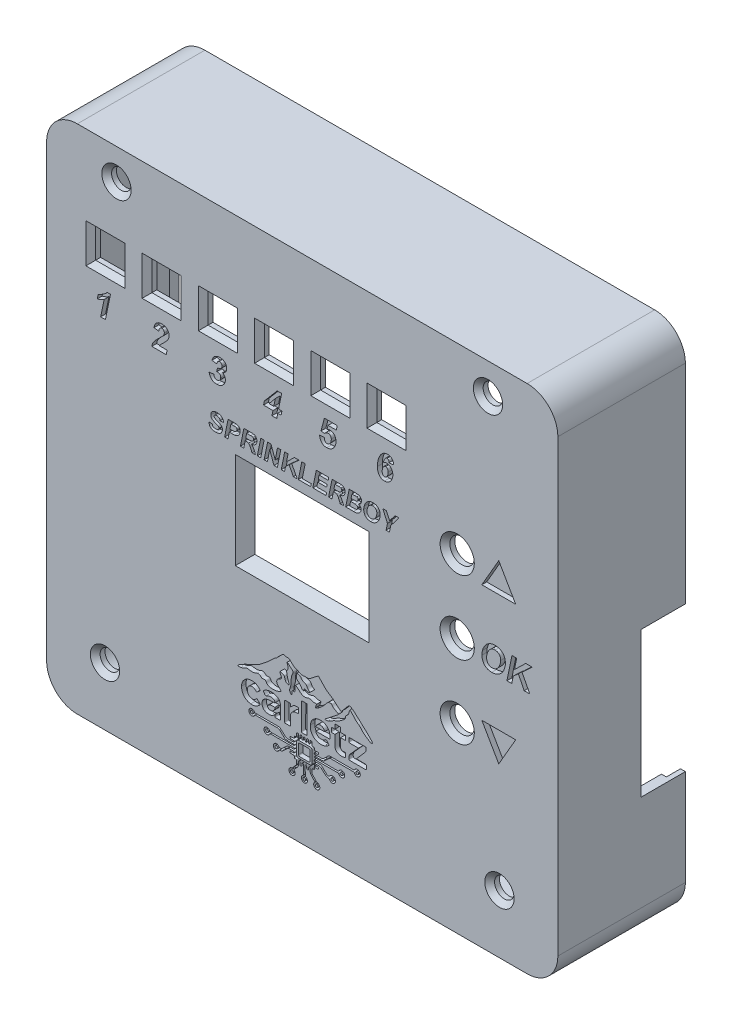
SolidWorks part; units mm, degrees
ref_plane "Front Plane" through (0, 0, 0) normal (0, 0, 1) x (1, 0, 0)
ref_plane "Top Plane" through (0, 0, 0) normal (0, 1, 0) x (1, 0, 0)
ref_plane "Right Plane" through (0, 0, 0) normal (1, 0, 0) x (0, 0, -1)
sketch "Sketch1" plane through (0, 0, 107.9354) normal (0, 0, 1) x (1, 0, 0)
  line L0 (-17.9008, 110.3032) -> (74.0994, 110.3032) construction
  line L1 (80.3867, 104.0159) -> (80.3867, 61.3601) construction
  line L2 (-24.1881, 12.0157) -> (-24.1881, 104.0159) construction
  line L3 (-13.5528, 5.7284) -> (-17.9008, 5.7284) construction
  line L6 (-17.9008, 110.3032) -> (74.0994, 110.3032)
  line L7 (80.3867, 104.0159) -> (80.3867, 61.3601)
  line L8 (-24.1881, 12.0157) -> (-24.1881, 104.0159)
  line L9 (-13.5528, 5.7284) -> (-17.9008, 5.7284)
  line L13 (80.3867, 31.6547) -> (80.3867, 12.0157) construction
  line L14 (80.3867, 31.6547) -> (80.3867, 12.0157)
  line L15 (-13.5528, 5.7284) -> (69.2377, 5.7284) construction
  line L16 (-13.5528, 5.7284) -> (69.2377, 5.7284)
  line L17 (80.3867, 31.6547) -> (80.3867, 61.3601) construction
  line L18 (80.3867, 31.6547) -> (80.3867, 61.3601)
  line L19 (74.0994, 5.7284) -> (69.2377, 5.7284) construction
  line L20 (74.0994, 5.7284) -> (69.2377, 5.7284)
  arc A0 (80.3867, 104.0159) -> (74.0994, 110.3032) centre (74.0994, 104.0159) ccw construction
  arc A1 (-17.9008, 110.3032) -> (-24.1881, 104.0159) centre (-17.9008, 104.0159) ccw construction
  arc A2 (-24.1881, 12.0157) -> (-17.9008, 5.7284) centre (-17.9008, 12.0157) ccw construction
  arc A4 (80.3867, 104.0159) -> (74.0994, 110.3032) centre (74.0994, 104.0159) ccw
  arc A5 (-17.9008, 110.3032) -> (-24.1881, 104.0159) centre (-17.9008, 104.0159) ccw
  arc A6 (-24.1881, 12.0157) -> (-17.9008, 5.7284) centre (-17.9008, 12.0157) ccw
  arc A8 (74.0994, 5.7284) -> (80.3867, 12.0157) centre (74.0994, 12.0157) ccw construction
  arc A9 (74.0994, 5.7284) -> (80.3867, 12.0157) centre (74.0994, 12.0157) ccw
extrude "Boss-Extrude1" add sketch "Sketch1" along normal blind 2
sketch "Sketch3" plane through (0, 0, 107.9354) normal (0, 0, -1) x (-1, 0, 0)
  line L13 (24.1881, 104.0159) -> (24.1881, 12.0157) construction
  line L14 (17.9008, 5.7284) -> (-74.0994, 5.7284) construction
  line L15 (-80.3867, 12.0157) -> (-80.3867, 104.0159) construction
  line L16 (-74.0994, 110.3032) -> (17.9008, 110.3032) construction
  line L17 (24.1881, 104.0159) -> (24.1881, 12.0157)
  line L18 (17.9008, 5.7284) -> (-74.0994, 5.7284)
  line L19 (-80.3867, 12.0157) -> (-80.3867, 104.0159)
  line L20 (-74.0994, 110.3032) -> (17.9008, 110.3032)
  line L21 (-74.0994, 108.3032) -> (17.9008, 108.3032)
  line L22 (22.1881, 104.0159) -> (22.1881, 12.0157)
  line L23 (17.9008, 7.7284) -> (-74.0994, 7.7284)
  line L24 (-78.3867, 12.0157) -> (-78.3867, 104.0159)
  arc A12 (24.1881, 104.0159) -> (17.9008, 110.3032) centre (17.9008, 104.0159) ccw construction
  arc A13 (17.9008, 5.7284) -> (24.1881, 12.0157) centre (17.9008, 12.0157) ccw construction
  arc A14 (-80.3867, 12.0157) -> (-74.0994, 5.7284) centre (-74.0994, 12.0157) ccw construction
  arc A15 (-74.0994, 110.3032) -> (-80.3867, 104.0159) centre (-74.0994, 104.0159) ccw construction
  arc A16 (24.1881, 104.0159) -> (17.9008, 110.3032) centre (17.9008, 104.0159) ccw
  arc A17 (17.9008, 5.7284) -> (24.1881, 12.0157) centre (17.9008, 12.0157) ccw
  arc A18 (-80.3867, 12.0157) -> (-74.0994, 5.7284) centre (-74.0994, 12.0157) ccw
  arc A19 (-74.0994, 110.3032) -> (-80.3867, 104.0159) centre (-74.0994, 104.0159) ccw
  arc A20 (22.1881, 104.0159) -> (17.9008, 108.3032) centre (17.9008, 104.0159) ccw
  arc A21 (17.9008, 7.7284) -> (22.1881, 12.0157) centre (17.9008, 12.0157) ccw
  arc A22 (-78.3867, 12.0157) -> (-74.0994, 7.7284) centre (-74.0994, 12.0157) ccw
  arc A23 (-74.0994, 108.3032) -> (-78.3867, 104.0159) centre (-74.0994, 104.0159) ccw
  dimension "D1" = 2
extrude "Boss-Extrude2" add sketch "Sketch3" along normal up to surface (21.1862 mm away)
sketch "Sketch4" plane through (0, 0, 109.9354) normal (0, 0, 1) x (1, 0, 0)
  circle A0 centre (-9.9008, 104.0159) radius 2
  circle A1 centre (66.0994, 104.0159) radius 2
  circle A2 centre (68.4425, 17.6725) radius 2
  circle A3 centre (-12.244, 17.6725) radius 1.998
extrude "Cut-Extrude1" cut sketch "Sketch4" against normal up to next
sketch "Sketch5" plane through (0, 0, 109.9354) normal (0, 0, 1) x (1, 0, 0)
  line L0 (39.2941, 65.3848) -> (16.9045, 65.3848) construction
  line L1 (16.9045, 65.3848) -> (39.2941, 65.3848)
  line L2 (16.9045, 65.3848) -> (16.9045, 50.6848)
  line L3 (16.9045, 50.6848) -> (39.2941, 50.6848)
  line L4 (39.2941, 65.3848) -> (39.2941, 50.6848)
  line L5 (16.9045, 65.3848) -> (16.9045, 50.6848) construction
  line L6 (16.9045, 50.6848) -> (39.2941, 50.6848) construction
extrude "Cut-Extrude2" cut sketch "Sketch5" against normal up to next
chamfer "Chamfer1" distance 2.5 angle 45 4 edges at (28.0993, 50.6848, 109.9354) (39.2941, 58.0348, 109.9354) (16.9045, 58.0348, 109.9354) (28.0993, 65.3848, 109.9354)
sketch "Sketch7" plane through (80.3867, 0, 0) normal (1, 0, 0) x (0, 0, -1)
  line L0 (-92.9354, 104.0159) -> (-92.9354, 12.0157) construction
  line L1 (-92.9354, 31.6547) -> (-75.9354, 31.6547)
  line L2 (-92.9354, 31.6547) -> (-92.9354, 61.3601)
  line L3 (-92.9354, 61.3601) -> (-75.9354, 61.3601)
  line L4 (-75.9354, 31.6547) -> (-75.9354, 61.3601)
  line L5 (-83.5354, 31.7547) -> (-91.3354, 31.7547) construction
  line L6 (-83.5354, 61.2601) -> (-91.3354, 61.2601) construction
  dimension "D1" = 17
  dimension "D2" = 0.1
  dimension "D3" = 0.1
extrude "Cut-Extrude4" cut sketch "Sketch7" against normal up to next
sketch "Sketch8" plane through (0, 5.7284, 0) normal (0, -1, 0) x (1, 0, 0)
  line L0 (74.0994, 86.7492) -> (-17.9008, 86.7492) construction
  line L1 (-13.5528, 86.7492) -> (51.7933, 86.7492)
  line L2 (-13.5528, 86.7492) -> (-13.5528, 90.2354)
  line L3 (-13.5528, 90.2354) -> (51.7933, 90.2354)
  line L4 (51.7933, 86.7492) -> (51.7933, 90.2354)
  line L5 (-13.5528, 83.7492) -> (-13.5528, 73.2354) construction
  line L6 (51.6933, 81.1633) -> (51.6933, 73.3354) construction
  line L7 (-13.5528, 73.2354) -> (69.2377, 73.2354) construction
  dimension "D1" = 0.1
  dimension "D2" = 17
extrude "Cut-Extrude5" cut sketch "Sketch8" against normal up to next and the other way through all
sketch "Sketch9" plane through (0, 0, 109.9354) normal (0, 0, 1) x (1, 0, 0)
  line L0 (-15.0508, 92.6158) -> (-15.0508, 87.4158) construction
  line L1 (-15.1508, 93.0158) -> (-9.1508, 93.0158)
  line L2 (-15.1508, 93.0158) -> (-15.1508, 87.0158)
  line L3 (-15.1508, 87.0158) -> (-9.1508, 87.0158)
  line L4 (-9.1508, 93.0158) -> (-9.1508, 87.0158)
  line L5 (-14.7508, 87.1158) -> (-9.5508, 87.1158) construction
  line L6 (-9.2508, 87.4158) -> (-9.2508, 92.6158) construction
  line L7 (-9.5508, 92.9158) -> (-14.7508, 92.9158) construction
  line L8 (1.9492, 92.9158) -> (-3.2508, 92.9158) construction
  line L9 (-3.6508, 93.0158) -> (2.3492, 93.0158)
  line L10 (-3.6508, 93.0158) -> (-3.6508, 87.0158)
  line L11 (-3.6508, 87.0158) -> (2.3492, 87.0158)
  line L12 (2.3492, 93.0158) -> (2.3492, 87.0158)
  line L13 (-3.5508, 92.6158) -> (-3.5508, 87.4158) construction
  line L14 (-3.2508, 87.1158) -> (1.9492, 87.1158) construction
  line L15 (2.2492, 87.4158) -> (2.2492, 92.6158) construction
  line L16 (7.9492, 92.6158) -> (7.9492, 87.4158) construction
  line L17 (7.8492, 93.0158) -> (13.8492, 93.0158)
  line L18 (7.8492, 93.0158) -> (7.8492, 87.0158)
  line L19 (7.8492, 87.0158) -> (13.8492, 87.0158)
  line L20 (13.8492, 93.0158) -> (13.8492, 87.0158)
  line L21 (13.4492, 92.9158) -> (8.2492, 92.9158) construction
  line L22 (13.7492, 87.4158) -> (13.7492, 92.6158) construction
  line L23 (8.2492, 87.1158) -> (13.4492, 87.1158) construction
  line L24 (24.9493, 92.9158) -> (19.7493, 92.9158) construction
  line L25 (19.3493, 93.0158) -> (25.3493, 93.0158)
  line L26 (19.3493, 93.0158) -> (19.3493, 87.0158)
  line L27 (19.3493, 87.0158) -> (25.3493, 87.0158)
  line L28 (25.3493, 93.0158) -> (25.3493, 87.0158)
  line L29 (19.4493, 92.6158) -> (19.4493, 87.4158) construction
  line L30 (19.7493, 87.1158) -> (24.9493, 87.1158) construction
  line L31 (25.2493, 87.4158) -> (25.2493, 92.6158) construction
  line L32 (36.4493, 92.9158) -> (31.2493, 92.9158) construction
  line L33 (30.8493, 93.0158) -> (36.8493, 93.0158)
  line L34 (30.8493, 93.0158) -> (30.8493, 87.0158)
  line L35 (30.8493, 87.0158) -> (36.8493, 87.0158)
  line L36 (36.8493, 93.0158) -> (36.8493, 87.0158)
  line L37 (42.3493, 93.0158) -> (48.3493, 93.0158)
  line L38 (42.3493, 93.0158) -> (42.3493, 87.0158)
  line L39 (42.3493, 87.0158) -> (48.3493, 87.0158)
  line L40 (48.3493, 93.0158) -> (48.3493, 87.0158)
  line L41 (36.7493, 87.4158) -> (36.7493, 92.6158) construction
  line L42 (31.2493, 87.1158) -> (36.4493, 87.1158) construction
  line L43 (30.9493, 92.6158) -> (30.9493, 87.4158) construction
  line L44 (42.4493, 92.6158) -> (42.4493, 87.4158) construction
  line L45 (42.7493, 87.1158) -> (47.9493, 87.1158) construction
  line L46 (48.2493, 87.4158) -> (48.2493, 92.6158) construction
  line L47 (47.9493, 92.9158) -> (42.7493, 92.9158) construction
  dimension "D1" = 0.1
  dimension "D2" = 0.1
  dimension "D3" = 0.1
  dimension "D4" = 0.1
  dimension "D5" = 0.1
  dimension "D6" = 0.1
  dimension "D7" = 0.1
  dimension "D8" = 0.1
  dimension "D9" = 0.1
  dimension "D10" = 0.1
  dimension "D11" = 0.1
  dimension "D12" = 0.1
  dimension "D13" = 0.1
  dimension "D14" = 0.1
  dimension "D15" = 0.1
  dimension "D16" = 0.1
  dimension "D17" = 0.1
  dimension "D18" = 0.1
  dimension "D19" = 0.1
  dimension "D20" = 0.1
  dimension "D21" = 0.1
  dimension "D22" = 0.1
  dimension "D23" = 0.1
  dimension "D24" = 0.1
extrude "Cut-Extrude6" cut sketch "Sketch9" against normal up to next
sketch "Sketch10" plane through (0, 0, 109.9354) normal (0, 0, 1) x (1, 0, 0)
  circle A0 centre (59.7974, 73.0158) radius 2.5
  circle A1 centre (59.7974, 58.0158) radius 2.5
  circle A2 centre (59.7974, 43.0157) radius 2.5
  arc A3 (62.4474, 75.2658) -> (63.6474, 75.2658) centre (63.0474, 75.2658) ccw construction
  arc A5 (57.1473, 60.2658) -> (55.9473, 60.2658) centre (56.5473, 60.2658) ccw construction
  arc A6 (62.4474, 60.2658) -> (63.6474, 60.2658) centre (63.0474, 60.2658) ccw construction
  arc A7 (57.1473, 40.7657) -> (55.9473, 40.7657) centre (56.5473, 40.7657) ccw construction
  arc A8 (63.6474, 40.7657) -> (62.4474, 40.7657) centre (63.0474, 40.7657) ccw construction
  dimension "D2" = 5
  dimension "D3" = 3.25
  dimension "D4" = 2.25
  dimension "D5" = 3.25
  dimension "D6" = 5
  dimension "D8" = 3.25
  dimension "D9" = 5
  dimension "D1" = 2.25
  dimension "D7" = 2.25
extrude "Cut-Extrude7" cut sketch "Sketch10" against normal up to next
chamfer "Chamfer2" distance 1 angle 45 3 edges at (62.2974, 43.0157, 109.9354) (62.2974, 58.0158, 109.9354) (62.2974, 73.0158, 109.9354)
chamfer "Chamfer3" distance 1 angle 45 24 edges at (48.3493, 90.0158, 109.9354) (45.3493, 93.0158, 109.9354) (42.3493, 90.0158, 109.9354) (45.3493, 87.0158, 109.9354) (33.8493, 87.0158, 109.9354) (36.8493, 90.0158, 109.9354) (33.8493, 93.0158, 109.9354) (30.8493, 90.0158, 109.9354) (25.3493, 90.0158, 109.9354) (22.3493, 93.0158, 109.9354) (19.3493, 90.0158, 109.9354) (22.3493, 87.0158, 109.9354) (10.8492, 87.0158, 109.9354) (13.8492, 90.0158, 109.9354) (10.8492, 93.0158, 109.9354) (7.8492, 90.0158, 109.9354) (2.3492, 90.0158, 109.9354) (-0.6508, 93.0158, 109.9354) (-3.6508, 90.0158, 109.9354) (-0.6508, 87.0158, 109.9354) (-12.1508, 87.0158, 109.9354) (-9.1508, 90.0158, 109.9354) (-12.1508, 93.0158, 109.9354) (-15.1508, 90.0158, 109.9354)
sketch "Sketch11" plane through (0, 0, 109.9354) normal (0, 0, 1) x (1, 0, 0)
  text T0 "OK" font "Arial" height 5
extrude "Cut-Extrude8" cut sketch "Sketch11" against normal blind 1
sketch "Sketch12" plane through (0, 0, 109.9354) normal (0, 0, 1) x (1, 0, 0)
  line L1 (68.2974, 76.0158) -> (64.8332, 70.0158)
  line L2 (64.8332, 70.0158) -> (71.7615, 70.0158)
  line L3 (71.7615, 70.0158) -> (68.2974, 76.0158)
  line L7 (68.2974, 40.0157) -> (71.7615, 46.0157)
  line L8 (71.7615, 46.0157) -> (64.8332, 46.0157)
  line L9 (64.8332, 46.0157) -> (68.2974, 40.0157)
  circle A0 centre (68.2974, 72.0158) radius 2 construction
  circle A1 centre (59.7974, 73.0158) radius 3.5 construction
  circle A2 centre (59.7974, 73.0158) radius 2.5 construction
  circle A4 centre (68.2974, 44.0157) radius 2 construction
  circle A5 centre (59.7974, 43.0157) radius 3.5 construction
  dimension "D2" = 3
  dimension "D1" = 6
  dimension "D3" = 8.5
  dimension "D4" = 6
  dimension "D5" = 3
  dimension "D6" = 8.5
extrude "Cut-Extrude9" cut sketch "Sketch12" against normal blind 1
sketch "Sketch13" plane through (0, 0, 109.9354) normal (0, 0, 1) x (1, 0, 0)
  text T0 "1" font "Arial" height 5
  text T1 "2" font "Arial" height 5
  text T2 "3" font "Arial" height 5
  text T3 "4" font "Arial" height 5
  text T4 "5" font "Arial" height 5
  text T5 "6" font "Arial" height 5
extrude "Cut-Extrude10" cut sketch "Sketch13" against normal blind 1
sketch "Sketch14" plane through (0, 0, 109.9354) normal (0, 0, 1) x (1, 0, 0)
  text T0 "SPRINKLERBOY" font "Arial" height 3.5
extrude "Cut-Extrude12" cut sketch "Sketch14" against normal blind 1
sketch "Schizzo3" plane through (0, 0, 109.9354) normal (0, 0, 1) x (1, 0, 0)
  spline S0 degree 3 poles (28.3707, 32.9624) (28.4003, 33.0508) (28.4309, 33.1328) (28.4554, 33.2167) (28.5202, 33.4376) (28.6287, 33.4812) (28.8265, 33.3629) (29.1577, 33.1648) (29.4064, 33.1809) (29.7538, 33.4451) knots 10 10 10 10 11 11 11 12 12 12 13 13 13 13
  spline S1 degree 3 poles (26.9936, 35.4214) (26.9837, 35.2643) (26.9839, 35.1121) (26.9628, 34.9628) (26.8906, 34.453) (26.9614, 34.2983) (27.4029, 34.0331) (27.4431, 34.0089) (27.487, 33.9828) (27.514, 33.9463) (27.6507, 33.7615) (27.792, 33.579) (27.9129, 33.3841) (28.0243, 33.2047) (28.1215, 33.0208) (28.3707, 32.9624) knots 5 5 5 5 6 6 6 7 7 7 8 8 8 9 9 9 10 10 10 10
  spline S2 degree 3 poles (29.7538, 33.4451) (29.6587, 33.5005) (29.5875, 33.5529) (29.5083, 33.5858) (29.3144, 33.6662) (29.1873, 33.8094) (29.1235, 34.0017) (29.0268, 34.2938) (28.8358, 34.4717) (28.5351, 34.5303) (28.2311, 34.5895) (28.0208, 34.7588) (27.865, 35.0288) (27.6895, 35.3328) (27.3113, 35.4806) (26.9936, 35.4214) knots 0 0 0 0 1 1 1 2 2 2 3 3 3 4 4 4 5 5 5 5
  spline S3 degree 3 poles (30.831, 31.2383) (30.8323, 31.2978) (30.8196, 31.3619) (30.8376, 31.4158) (30.894, 31.5846) (30.9619, 31.7496) (31.0421, 31.9596) knots 117 117 117 117 118 118 118 119 119 119 119
  spline S4 degree 3 poles (32.6948, 30.1787) (32.9278, 30.3418) (33.1268, 30.4678) (33.3111, 30.6126) (33.9753, 31.1341) (34.6377, 31.6579) (35.294, 32.1893) (35.5595, 32.4043) (35.5368, 32.4708) (35.2345, 32.6224) (34.9868, 32.7465) (34.7415, 32.882) (34.5168, 33.0428) (34.3753, 33.1441) (34.2606, 33.2919) (34.1587, 33.4363) (34.0838, 33.5424) (34.0024, 33.5842) (33.8814, 33.5706) (33.5343, 33.5316) (33.2487, 33.381) (33.0363, 33.1007) (32.9598, 32.9998) (32.895, 32.8893) (32.8122, 32.7942) (32.6712, 32.6322) (32.5268, 32.472) (32.3719, 32.3234) (32.1247, 32.0861) (31.8767, 31.8482) (31.612, 31.6312) (31.431, 31.4829) (31.2245, 31.3642) (31.0219, 31.2451) (30.9737, 31.2167) (30.8954, 31.2392) (30.831, 31.2383) knots 105 105 105 105 106 106 106 107 107 107 108 108 108 109 109 109 110 110 110 111 111 111 112 112 112 113 113 113 114 114 114 115 115 115 116 116 116 117 117 117 117
  spline S5 degree 3 poles (37.8726, 34.3603) (37.8012, 34.174) (37.7274, 34.04) (37.6995, 33.897) (37.633, 33.5555) (37.4795, 33.2818) (37.1986, 33.0664) (37.0944, 32.9864) (36.9837, 32.8424) (36.9766, 32.7216) (36.954, 32.341) (36.7284, 32.1032) (36.467, 31.8835) (35.9887, 31.4816) (35.4676, 31.1584) (34.8747, 30.938) (34.5034, 30.8) (34.1637, 30.5761) (33.8117, 30.3873) (33.5272, 30.2347) (33.2382, 30.0971) (32.9057, 30.105) (32.8479, 30.1064) (32.7911, 30.1438) (32.6948, 30.1787) knots 97 97 97 97 98 98 98 99 99 99 100 100 100 101 101 101 102 102 102 103 103 103 104 104 104 105 105 105 105
  spline S6 degree 3 poles (31.3954, 37.1477) (31.7741, 36.7468) (32.1481, 36.3525) (32.5203, 35.9566) (32.9469, 35.5029) (33.4309, 35.1296) (33.9813, 34.8319) (34.2372, 34.6935) (34.4614, 34.4905) (34.6844, 34.2987) (35.0525, 33.982) (35.4011, 33.6424) (35.7714, 33.3285) (35.9749, 33.156) (36.0519, 33.1572) (36.2299, 33.3549) (36.4941, 33.6484) (36.7256, 33.9712) (36.9797, 34.2743) (37.1593, 34.4887) (37.3469, 34.6973) (37.5427, 34.8969) (37.6919, 35.0489) (37.8383, 35.0762) (38.0153, 34.9617) (38.2891, 34.7847) (38.5633, 34.6009) (38.8059, 34.3846) (39.6068, 33.6705) (40.3977, 32.9449) (41.1839, 32.2145) (41.5158, 31.9061) (41.8292, 31.5777) (42.1448, 31.2522) (42.2505, 31.1432) (42.348, 31.0223) (42.4291, 30.894) (42.5195, 30.7511) (42.4534, 30.6351) (42.2881, 30.6449) (42.1704, 30.6518) (42.0371, 30.6677) (41.9413, 30.728) (41.3164, 31.1219) (40.6855, 31.513) (40.1911, 32.0743) (39.9962, 32.2955) (39.8402, 32.55) (39.5805, 32.7098) (39.4147, 32.8118) (39.2326, 32.9024) (39.0989, 33.0386) (38.8189, 33.3238) (38.5689, 33.6384) (38.3006, 33.9355) (38.1789, 34.0703) (38.0429, 34.1923) (37.8726, 34.3603) knots 78 78 78 78 79 79 79 80 80 80 81 81 81 82 82 82 83 83 83 84 84 84 85 85 85 86 86 86 87 87 87 88 88 88 89 89 89 90 90 90 91 91 91 92 92 92 93 93 93 94 94 94 95 95 95 96 96 96 97 97 97 97
  spline S7 degree 3 number of poles 172 (25.0103, 36.3727) -> (31.3954, 37.1477)
  spline S8 degree 3 poles (25.9032, 31.065) (25.5886, 31.2528) (25.4281, 31.6472) (25.5642, 31.9828) (25.742, 32.4214) (25.8228, 32.8688) (25.7908, 33.3403) (25.7837, 33.4437) (25.8098, 33.5495) (25.8227, 33.6539) (25.8531, 33.8991) (25.8653, 34.1486) (25.9218, 34.3876) (25.968, 34.5835) (26.0591, 34.7706) (26.1453, 34.9546) (26.2792, 35.2402) (26.2673, 35.3458) (26.0378, 35.5504) (25.7777, 35.7823) (25.5166, 36.013) (25.2516, 36.2392) (25.196, 36.2866) (25.1217, 36.3122) (25.0103, 36.3727) knots 13 13 13 13 14 14 14 15 15 15 16 16 16 17 17 17 18 18 18 19 19 19 20 20 20 21 21 21 21
  spline S9 degree 3 poles (26.223, 32.0099) (26.03, 31.8279) (25.9736, 31.6084) (26.0018, 31.3591) (26.0144, 31.2469) (26.0236, 31.1337) (25.9032, 31.065) knots 11 11 11 11 12 12 12 13 13 13 13
  spline S10 degree 3 poles (31.0421, 31.9596) (30.9082, 31.9759) (30.7944, 32.0097) (30.6851, 31.9987) (30.4678, 31.9768) (30.2632, 32.0052) (30.0704, 32.1015) (29.7739, 32.2496) (29.4735, 32.2673) (29.1711, 32.1341) (28.5234, 31.8488) (28.0101, 32.0981) (27.5349, 32.5282) (27.3394, 32.7052) (27.1395, 32.8791) (26.9285, 33.0369) (26.7405, 33.1775) (26.629, 33.1179) (26.6158, 32.8795) (26.6056, 32.6949) (26.6168, 32.5092) (26.6113, 32.3242) (26.6078, 32.2084) (26.6009, 32.0909) (26.576, 31.9785) (26.5631, 31.9204) (26.5107, 31.8312) (26.471, 31.8283) (26.4139, 31.8242) (26.3495, 31.8824) (26.2935, 31.9215) (26.265, 31.9413) (26.248, 31.9775) (26.223, 32.0099) knots 0 0 0 0 1 1 1 2 2 2 3 3 3 4 4 4 5 5 5 6 6 6 7 7 7 8 8 8 9 9 9 10 10 10 11 11 11 11
  spline S11 degree 3 poles (28.8018, 17.4103) (28.7954, 17.5593) (28.6614, 17.6925) (28.5116, 17.6867) (28.3723, 17.6813) (28.226, 17.608) (28.2541, 17.4266) knots 2 2 2 2 3 3 3 4 4 4 4
  spline S12 degree 3 poles (28.2541, 17.4266) (28.2562, 17.2617) (28.3812, 17.1212) (28.5263, 17.1206) (28.672, 17.1199) (28.8082, 17.2632) (28.8018, 17.4103) knots 0 0 0 0 1 1 1 2 2 2 2
  spline S13 degree 3 poles (22.8204, 19.942) (22.9551, 19.9451) (23.1, 20.0979) (23.0973, 20.2339) (23.0946, 20.3712) (22.9456, 20.5154) (22.808, 20.5137) knots 2 2 2 2 3 3 3 4 4 4 4
  spline S14 degree 3 poles (22.808, 20.5137) (22.6576, 20.5119) (22.5462, 20.3861) (22.5483, 20.2207) (22.5505, 20.055) (22.6644, 19.9383) (22.8204, 19.942) knots 0 0 0 0 1 1 1 2 2 2 2
  spline S15 degree 3 poles (20.613, 22.1633) (20.6143, 22.0216) (20.7553, 21.8784) (20.8941, 21.8779) (21.0477, 21.8773) (21.1819, 22.0023) (21.1848, 22.1487) knots 2 2 2 2 3 3 3 4 4 4 4
  spline S16 degree 3 poles (21.1848, 22.1487) (21.1877, 22.2941) (21.0391, 22.4515) (20.9, 22.4503) (20.7755, 22.4493) (20.6118, 22.2856) (20.613, 22.1633) knots 0 0 0 0 1 1 1 2 2 2 2
  spline S17 degree 3 poles (30.8017, 17.4972) (30.8032, 17.333) (30.9173, 17.213) (31.0734, 17.2117) (31.2166, 17.2106) (31.3422, 17.3453) (31.3441, 17.5023) (31.3459, 17.6554) (31.2189, 17.784) (31.0661, 17.7837) knots 1 1 1 1 2 2 2 3 3 3 4 4 4 4
  spline S18 degree 3 poles (31.0661, 17.7837) (30.9098, 17.7834) (30.8002, 17.6646) (30.8017, 17.4972) knots 0 0 0 0 1 1 1 1
  spline S19 degree 3 poles (25.7242, 17.5144) (25.7193, 17.3486) (25.8416, 17.2118) (25.9945, 17.2118) (26.1422, 17.2118) (26.267, 17.3403) (26.2694, 17.495) knots 2 2 2 2 3 3 3 4 4 4 4
  spline S20 degree 3 poles (26.2694, 17.495) (26.2721, 17.664) (26.1684, 17.7794) (26.009, 17.785) (25.8567, 17.7902) (25.7287, 17.6686) (25.7242, 17.5144) knots 0 0 0 0 1 1 1 2 2 2 2
  spline S21 degree 3 poles (17.7955, 23.6252) (17.9366, 23.6237) (18.0756, 23.7618) (18.0783, 23.9062) (18.0815, 24.0786) (17.9685, 24.1986) (17.8013, 24.2005) knots 2 2 2 2 3 3 3 4 4 4 4
  spline S22 degree 3 poles (17.8013, 24.2005) (17.6517, 24.2022) (17.5347, 24.0877) (17.5309, 23.936) (17.5267, 23.7705) (17.6491, 23.6268) (17.7955, 23.6252) knots 0 0 0 0 1 1 1 2 2 2 2
  spline S23 degree 3 poles (36.1356, 22.4502) (36.0133, 22.4491) (35.8552, 22.2846) (35.8535, 22.1567) (35.8516, 22.014) (35.9874, 21.8799) (36.1372, 21.8765) knots 2 2 2 2 3 3 3 4 4 4 4
  spline S24 degree 3 poles (36.1372, 21.8765) (36.2785, 21.8733) (36.4194, 22.0092) (36.4237, 22.1528) (36.4281, 22.3007) (36.2819, 22.4517) (36.1356, 22.4502) knots 0 0 0 0 1 1 1 2 2 2 2
  spline S25 degree 3 poles (39.6229, 23.9255) (39.6216, 24.0626) (39.489, 24.192) (39.3448, 24.1969) (39.1887, 24.2023) (39.0612, 24.0733) (39.0588, 23.9076) knots 2 2 2 2 3 3 3 4 4 4 4
  spline S26 degree 3 poles (39.0588, 23.9076) (39.0568, 23.7659) (39.1903, 23.6276) (39.3335, 23.6233) (39.4645, 23.6193) (39.6243, 23.7862) (39.6229, 23.9255) knots 0 0 0 0 1 1 1 2 2 2 2
  spline S27 degree 3 poles (34.264, 20.5138) (34.1348, 20.5107) (33.9378, 20.3416) (33.9415, 20.2369) (33.9459, 20.1147) (34.1348, 19.9417) (34.2644, 19.9413) knots 2 2 2 2 3 3 3 4 4 4 4
  spline S28 degree 3 poles (34.2644, 19.9413) (34.4003, 19.9409) (34.5462, 20.0833) (34.5504, 20.2205) (34.555, 20.3703) (34.4114, 20.5174) (34.264, 20.5138) knots 0 0 0 0 1 1 1 2 2 2 2
  spline S29 degree 3 poles (30.0964, 21.3289) (30.0963, 21.969) (30.098, 22.6091) (30.0958, 23.2492) (30.0948, 23.5552) (29.9275, 23.7212) (29.627, 23.7215) (28.8864, 23.7224) (28.1458, 23.7241) (27.4051, 23.7221) (27.1324, 23.7214) (26.9628, 23.5471) (26.9622, 23.2759) (26.9614, 22.8898) (26.962, 22.5036) (26.9621, 22.1174) knots 5 5 5 5 6 6 6 7 7 7 8 8 8 9 9 9 10 10 10 10
  spline S30 degree 3 poles (26.9621, 22.1174) (26.9621, 21.7417) (26.9612, 21.3661) (26.9623, 20.9905) (26.9632, 20.7074) (27.1203, 20.541) (27.3977, 20.5402) (28.1542, 20.5381) (28.9107, 20.5389) (29.6672, 20.5421) (29.9317, 20.5431) (30.0883, 20.699) (30.098, 20.9639) (30.1025, 21.0854) (30.0965, 21.2072) (30.0964, 21.3289) knots 0 0 0 0 1 1 1 2 2 2 3 3 3 4 4 4 5 5 5 5
  spline S31 degree 3 poles (31.1925, 18.134) (31.4324, 18.0711) (31.6546, 17.8443) (31.6913, 17.6133) (31.7343, 17.342) (31.6082, 17.07) (31.3781, 16.938) (31.1661, 16.8164) (30.8748, 16.8372) (30.6772, 16.988) (30.4122, 17.1904) (30.3583, 17.5677) (30.5556, 17.8504) (30.5916, 17.9019) (30.6344, 17.9487) (30.6935, 18.0218) knots 199 199 199 199 200 200 200 201 201 201 202 202 202 203 203 203 204 204 204 204
  spline S32 degree 3 poles (31.4647, 20.7845) (31.4655, 20.6593) (31.3736, 20.5919) (31.2589, 20.5841) (31.1223, 20.5749) (30.984, 20.5847) (30.8468, 20.5929) (30.6049, 20.6073) (30.5825, 20.5887) (30.5815, 20.3482) (30.5807, 20.151) (30.5422, 20.1138) (30.3358, 20.1194) (30.1943, 20.1233) (30.1016, 20.0822) (30.1, 19.9171) (30.0981, 19.7273) (30.0643, 19.5358) (30.0821, 19.3486) (30.0921, 19.243) (30.1602, 19.1291) (30.2327, 19.0455) (30.4752, 18.7661) (30.7281, 18.4954) (30.9853, 18.2295) (31.0348, 18.1783) (31.1194, 18.1532) (31.1925, 18.134) knots 190 190 190 190 191 191 191 192 192 192 193 193 193 194 194 194 195 195 195 196 196 196 197 197 197 198 198 198 199 199 199 199
  spline S33 degree 3 number of poles 94 (30.5743, 22.4263) -> (31.4647, 20.7845)
  spline S34 degree 3 number of poles 76 (31.2431, 23.569) -> (30.5743, 22.4263)
  spline S35 degree 3 poles (29.5528, 24.1641) (29.5996, 24.2155) (29.6757, 24.2612) (29.6869, 24.3194) (29.7084, 24.4317) (29.6959, 24.5511) (29.6927, 24.6674) (29.6888, 24.8052) (29.7506, 24.8994) (29.8864, 24.9104) (30.0361, 24.9225) (30.0838, 24.8125) (30.0908, 24.6841) (30.0986, 24.5416) (30.1025, 24.3988) (30.1039, 24.2562) (30.1052, 24.1266) (30.1573, 24.0656) (30.296, 24.0675) (30.5596, 24.0711) (30.5744, 24.0493) (30.5651, 23.7746) (30.5597, 23.6139) (30.6035, 23.5664) (30.7672, 23.5651) (30.9258, 23.5639) (31.0845, 23.565) (31.2431, 23.569) knots 125 125 125 125 126 126 126 127 127 127 128 128 128 129 129 129 130 130 130 131 131 131 132 132 132 133 133 133 134 134 134 134
  spline S36 degree 3 poles (28.8596, 24.148) (29.0017, 24.1446) (29.0045, 24.2574) (29.003, 24.3622) (29.0015, 24.468) (28.9962, 24.5739) (28.9985, 24.6796) (29.002, 24.8358) (29.0799, 24.9253) (29.2065, 24.9268) (29.3351, 24.9283) (29.4047, 24.8442) (29.4071, 24.68) (29.4088, 24.5583) (29.3924, 24.4338) (29.4142, 24.3161) (29.4248, 24.2589) (29.5044, 24.2144) (29.5528, 24.1641) knots 119 119 119 119 120 120 120 121 121 121 122 122 122 123 123 123 124 124 124 125 125 125 125
  spline S37 degree 3 poles (28.1782, 24.1625) (28.3086, 24.1583) (28.3262, 24.2572) (28.3275, 24.3589) (28.3289, 24.47) (28.3297, 24.5812) (28.3275, 24.6923) (28.3252, 24.8107) (28.3765, 24.885) (28.497, 24.896) (28.6296, 24.9082) (28.6941, 24.8267) (28.7056, 24.709) (28.7168, 24.5937) (28.7133, 24.4762) (28.7071, 24.3601) (28.7009, 24.244) (28.7316, 24.151) (28.8596, 24.148) knots 113 113 113 113 114 114 114 115 115 115 116 116 116 117 117 117 118 118 118 119 119 119 119
  spline S38 degree 3 number of poles 226 (26.8356, 19.07) -> (28.1782, 24.1625)
  spline S39 degree 3 poles (25.5109, 17.0952) (25.3516, 17.2988) (25.3228, 17.5273) (25.4381, 17.7621) (25.5379, 17.9652) (25.6844, 18.1111) (25.9248, 18.1474) (25.9951, 18.1581) (26.0715, 18.2084) (26.1211, 18.2626) (26.3636, 18.5277) (26.5975, 18.8008) (26.8356, 19.07) knots 34 34 34 34 35 35 35 36 36 36 37 37 37 38 38 38 38
  spline S40 degree 3 poles (26.3624, 18.0345) (26.5429, 17.8665) (26.65, 17.6729) (26.6211, 17.4221) (26.5891, 17.1443) (26.4324, 16.9725) (26.1761, 16.8855) (25.9355, 16.8038) (25.6779, 16.8818) (25.5109, 17.0952) knots 31 31 31 31 32 32 32 33 33 33 34 34 34 34
  spline S41 degree 3 poles (27.4857, 20.0978) (27.3662, 20.1023) (27.3438, 20.0094) (27.337, 19.9134) (27.3337, 19.866) (27.3234, 19.8169) (27.3316, 19.7713) (27.4169, 19.3003) (27.2425, 18.9265) (26.911, 18.6043) (26.7256, 18.424) (26.5517, 18.2319) (26.3624, 18.0345) knots 27 27 27 27 28 28 28 29 29 29 30 30 30 31 31 31 31
  spline S42 degree 3 poles (27.8482, 19.4014) (27.7298, 19.394) (27.6392, 19.4848) (27.6308, 19.6228) (27.6253, 19.7124) (27.6306, 19.8027) (27.6292, 19.8926) (27.6276, 19.993) (27.6124, 20.0931) (27.4857, 20.0978) knots 24 24 24 24 25 25 25 26 26 26 27 27 27 27
  spline S43 degree 3 poles (28.3356, 16.8124) (28.0998, 16.8814) (27.9571, 17.0557) (27.9152, 17.2994) (27.8707, 17.5579) (27.9526, 17.7757) (28.1783, 17.9136) (28.2946, 17.9848) (28.3307, 18.0672) (28.3298, 18.1956) (28.3262, 18.7406) (28.3303, 19.2856) (28.3311, 19.8306) (28.3312, 19.8781) (28.3439, 19.9355) (28.3221, 19.9708) (28.2904, 20.0223) (28.2251, 20.0981) (28.188, 20.091) (28.1331, 20.0805) (28.0605, 20.0126) (28.049, 19.9579) (28.0265, 19.8514) (28.0435, 19.737) (28.0399, 19.626) (28.0359, 19.5018) (27.9874, 19.4102) (27.8482, 19.4014) knots 15 15 15 15 16 16 16 17 17 17 18 18 18 19 19 19 20 20 20 21 21 21 22 22 22 23 23 23 24 24 24 24
  spline S44 degree 3 poles (29.0118, 19.6051) (29.0049, 19.6997) (29.0103, 19.795) (29.0075, 19.89) (29.0045, 19.9908) (28.9844, 20.0924) (28.8612, 20.097) (28.7347, 20.1017) (28.7103, 19.9988) (28.71, 19.8994) (28.7078, 19.3068) (28.7055, 18.7141) (28.7144, 18.1216) (28.7154, 18.0616) (28.7787, 17.9839) (28.8346, 17.9463) (29.1824, 17.7122) (29.2546, 17.2449) (28.979, 16.9577) (28.797, 16.768) (28.5689, 16.7442) (28.3356, 16.8124) knots 8 8 8 8 9 9 9 10 10 10 11 11 11 12 12 12 13 13 13 14 14 14 15 15 15 15
  spline S45 degree 3 poles (29.2196, 19.401) (29.0766, 19.3913) (29.0209, 19.4795) (29.0118, 19.6051) knots 7 7 7 7 8 8 8 8
  spline S46 degree 3 poles (29.4126, 19.9265) (29.3917, 19.8305) (29.4071, 19.7266) (29.4077, 19.6261) (29.4084, 19.4978) (29.3582, 19.4103) (29.2196, 19.401) knots 5 5 5 5 6 6 6 7 7 7 7
  spline S47 degree 3 poles (29.5379, 20.092) (29.4837, 20.0778) (29.4265, 19.9901) (29.4126, 19.9265) knots 4 4 4 4 5 5 5 5
  spline S48 degree 3 poles (30.6935, 18.0218) (30.4721, 18.2592) (30.2614, 18.4957) (30.0389, 18.7206) (29.8071, 18.9549) (29.6837, 19.2257) (29.6986, 19.5584) (29.7043, 19.685) (29.7002, 19.8124) (29.6929, 19.9389) (29.6874, 20.0326) (29.6366, 20.1178) (29.5379, 20.092) knots 0 0 0 0 1 1 1 2 2 2 3 3 3 4 4 4 4
  spline S49 degree 3 poles (21.5248, 26.1646) (22.0345, 26.1274) (22.5659, 26.5802) (22.502, 27.1381) knots 4 4 4 4 5 5 5 5
  spline S50 degree 3 poles (22.502, 27.1381) (22.3266, 27.1381) (22.1569, 27.1527) (21.9907, 27.1344) (21.7732, 27.1106) (21.5505, 27.0841) (21.3459, 27.0128) (21.2326, 26.9734) (21.1095, 26.8576) (21.0644, 26.7464) (20.9428, 26.4465) (21.1634, 26.191) (21.5248, 26.1646) knots 0 0 0 0 1 1 1 2 2 2 3 3 3 4 4 4 4
  spline S51 degree 3 poles (22.5043, 27.9307) (22.5531, 28.2057) (22.3386, 28.4741) (21.9804, 28.5452) (21.5637, 28.6281) (21.1755, 28.5585) (20.8132, 28.3342) (20.6307, 28.2212) (20.5462, 28.2437) (20.4189, 28.4218) (20.3392, 28.5334) (20.2576, 28.6437) (20.179, 28.756) (20.11, 28.8546) (20.1187, 28.9341) (20.2255, 29.0091) (20.9782, 29.5378) (21.7979, 29.6413) (22.6618, 29.3683) (23.2986, 29.167) (23.6604, 28.6342) (23.6605, 27.9659) (23.6607, 27.1725) (23.6576, 26.3791) (23.6632, 25.5857) (23.6643, 25.4321) (23.6209, 25.3629) (23.4576, 25.3673) (23.2146, 25.3739) (22.9712, 25.3645) (22.7279, 25.3605) (22.6016, 25.3584) (22.5444, 25.4173) (22.5493, 25.5444) (22.5535, 25.6553) (22.5501, 25.7664) (22.5501, 25.9051) knots 4 4 4 4 5 5 5 6 6 6 7 7 7 8 8 8 9 9 9 10 10 10 11 11 11 12 12 12 13 13 13 14 14 14 15 15 15 16 16 16 16
  spline S52 degree 3 poles (22.5501, 25.9051) (22.0288, 25.2356) (21.2597, 25.1911) (20.6364, 25.4043) (20.1813, 25.56) (19.9059, 25.9815) (19.8785, 26.4515) (19.8282, 27.3147) (20.4444, 27.7121) (21.0522, 27.8084) (21.5279, 27.8838) (22.0142, 27.892) (22.5043, 27.9307) knots 0 0 0 0 1 1 1 2 2 2 3 3 3 4 4 4 4
  spline S53 degree 3 poles (30.9209, 27.8862) (31.4912, 27.8862) (32.0611, 27.8862) (32.6409, 27.8862) knots 2 2 2 2 3 3 3 3
  spline S54 degree 3 poles (32.6409, 27.8862) (32.6083, 28.3419) (32.3044, 28.6071) (31.8191, 28.619) (31.3465, 28.6307) (30.9781, 28.3318) (30.9209, 27.8862) knots 0 0 0 0 1 1 1 2 2 2 2
  spline S55 degree 3 poles (29.7696, 27.636) (29.8077, 28.1304) (29.9867, 28.5691) (30.3409, 28.9219) (30.808, 29.3873) (31.3838, 29.5545) (32.0314, 29.51) (32.4876, 29.4787) (32.89, 29.3283) (33.2237, 29.0042) (33.5773, 28.6609) (33.7249, 28.2336) (33.7553, 27.7558) (33.7634, 27.6294) (33.7577, 27.5021) (33.7568, 27.3751) (33.7552, 27.1508) (33.7215, 27.1155) (33.5018, 27.1152) (32.735, 27.1141) (31.9682, 27.1142) (31.2014, 27.1139) (31.1066, 27.1139) (31.0118, 27.1139) (30.906, 27.1139) knots 8 8 8 8 9 9 9 10 10 10 11 11 11 12 12 12 13 13 13 14 14 14 15 15 15 16 16 16 16
  spline S56 degree 3 poles (30.906, 27.1139) (30.9484, 26.6154) (31.3544, 26.2513) (31.858, 26.2275) (32.2117, 26.2107) (32.521, 26.3142) (32.7972, 26.5315) (32.9479, 26.65) (33.002, 26.6441) (33.1321, 26.5078) (33.2562, 26.3778) (33.3783, 26.2457) (33.5044, 26.1177) (33.5906, 26.0302) (33.5799, 25.9587) (33.4925, 25.8767) (32.9726, 25.3894) (32.3518, 25.2238) (31.6559, 25.2929) (31.1647, 25.3417) (30.7275, 25.5106) (30.3647, 25.8575) (29.8526, 26.3471) (29.7175, 26.9611) (29.7696, 27.636) knots 0 0 0 0 1 1 1 2 2 2 3 3 3 4 4 4 5 5 5 6 6 6 7 7 7 8 8 8 8
  spline S57 degree 3 poles (39.605, 28.4512) (39.4532, 28.4512) (39.324, 28.4511) (39.1948, 28.4512) (38.7504, 28.4516) (38.3059, 28.456) (37.8616, 28.4502) (37.7105, 28.4483) (37.6528, 28.5024) (37.66, 28.6547) (37.6695, 28.8552) (37.6654, 29.0567) (37.6605, 29.2576) (37.6579, 29.3661) (37.6975, 29.4063) (37.8089, 29.4056) (38.8511, 29.3983) (39.8933, 29.3966) (40.9355, 29.39) (41.155, 29.3886) (41.1557, 29.3817) (41.1558, 29.1659) (41.1558, 29.15) (41.1558, 29.1342) (41.1558, 29.1183) (41.1552, 28.5946) (41.1508, 28.5985) (40.8043, 28.2113) (40.3004, 27.6481) (39.8034, 27.0788) (39.3041, 26.5116) (39.2664, 26.4689) (39.2333, 26.4221) (39.1729, 26.3452) knots 10 10 10 10 11 11 11 12 12 12 13 13 13 14 14 14 15 15 15 16 16 16 17 17 17 18 18 18 19 19 19 20 20 20 21 21 21 21
  spline S58 degree 3 poles (39.1729, 26.3452) (39.79, 26.3452) (40.3714, 26.3467) (40.9529, 26.3446) (41.2148, 26.3437) (41.2183, 26.337) (41.2188, 26.0808) (41.2191, 25.9168) (41.2201, 25.7528) (41.2201, 25.5888) (41.22, 25.4096) (41.1915, 25.3784) (41.0094, 25.3778) (40.6867, 25.3769) (40.364, 25.3806) (40.0413, 25.3813) (39.3271, 25.3828) (38.613, 25.3836) (37.8988, 25.3849) (37.66, 25.3854) (37.6572, 25.4139) (37.6316, 25.6453) (37.5844, 26.0717) (37.7271, 26.3897) (38.0311, 26.6973) (38.5616, 27.2343) (39.0456, 27.8173) (39.549, 28.3812) (39.5621, 28.3959) (39.5737, 28.412) (39.605, 28.4512) knots 0 0 0 0 1 1 1 2 2 2 3 3 3 4 4 4 5 5 5 6 6 6 7 7 7 8 8 8 9 9 9 10 10 10 10
  spline S59 degree 3 poles (17.5751, 25.288) (17.1011, 25.3364) (16.6741, 25.5072) (16.3255, 25.8367) (15.8745, 26.2629) (15.684, 26.8009) (15.6863, 27.4904) knots 14 14 14 14 15 15 15 16 16 16 16
  spline S60 degree 3 poles (17.2645, 26.5462) (17.6456, 26.2285) (18.1901, 26.2637) (18.5869, 26.632) (18.6256, 26.6679) (18.6628, 26.7056) (18.6993, 26.7438) (18.7819, 26.8302) (18.8616, 26.8248) (18.9438, 26.7418) (19.0964, 26.5879) (19.248, 26.4328) (19.4052, 26.2836) (19.5039, 26.1898) (19.4949, 26.0943) (19.4147, 26.0061) (18.921, 25.463) (18.3094, 25.213) (17.5751, 25.288) knots 8 8 8 8 9 9 9 10 10 10 11 11 11 12 12 12 13 13 13 14 14 14 14
  spline S61 degree 3 poles (15.6863, 27.4904) (15.6523, 28.3972) (16.3748, 29.3348) (17.4401, 29.4908) (18.1808, 29.5993) (18.8289, 29.3977) (19.3475, 28.8388) (19.5259, 28.6466) (19.5199, 28.5739) (19.3165, 28.4076) (19.1898, 28.3041) (19.058, 28.2067) (18.9333, 28.1009) (18.8106, 27.9967) (18.7119, 27.9932) (18.6002, 28.1258) (18.4515, 28.3022) (18.2618, 28.4291) (18.0335, 28.4813) (17.572, 28.5869) (17.1466, 28.3455) (16.9659, 27.8821) (16.7839, 27.4153) (16.9126, 26.8395) (17.2645, 26.5462) knots 0 0 0 0 1 1 1 2 2 2 3 3 3 4 4 4 5 5 5 6 6 6 7 7 7 8 8 8 8
  spline S62 degree 3 poles (36.8236, 25.3852) (36.6201, 25.3376) (36.4096, 25.305) (36.2008, 25.298) (35.7931, 25.2843) (35.4, 25.336) (35.086, 25.6421) (34.8733, 25.8494) (34.7759, 26.1027) (34.7743, 26.3931) (34.7707, 27.0331) (34.7732, 27.6732) (34.7732, 28.3132) (34.7732, 28.3683) (34.7732, 28.4234) (34.7732, 28.4831) knots 22 22 22 22 23 23 23 24 24 24 25 25 25 26 26 26 27 27 27 27
  spline S63 degree 3 poles (36.7828, 26.3831) (36.9106, 26.3899) (36.9838, 26.3212) (36.9878, 26.1958) (36.9945, 25.9844) (37.0052, 25.7715) (36.9856, 25.5619) (36.9795, 25.4962) (36.8903, 25.4008) (36.8236, 25.3852) knots 19 19 19 19 20 20 20 21 21 21 22 22 22 22
  spline S64 degree 3 poles (35.9478, 28.4827) (35.9478, 28.4193) (35.9478, 28.3635) (35.9478, 28.3078) (35.9479, 27.8265) (35.9565, 27.345) (35.9455, 26.8639) (35.9347, 26.3947) (36.2024, 26.2324) (36.6468, 26.3445) (36.6926, 26.3561) (36.737, 26.3807) (36.7828, 26.3831) knots 15 15 15 15 16 16 16 17 17 17 18 18 18 19 19 19 19
  spline S65 degree 3 poles (35.9478, 29.41) (36.2432, 29.41) (36.5221, 29.4051) (36.8008, 29.4121) (36.9437, 29.4157) (37.0024, 29.3672) (36.9938, 29.219) (36.9833, 29.0398) (36.9888, 28.8595) (36.9912, 28.6797) (36.993, 28.5436) (36.9418, 28.4765) (36.794, 28.4805) (36.5197, 28.488) (36.245, 28.4827) (35.9478, 28.4827) knots 10 10 10 10 11 11 11 12 12 12 13 13 13 14 14 14 15 15 15 15
  spline S66 degree 3 poles (34.7732, 29.406) (34.7732, 29.6412) (34.7731, 29.8713) (34.7733, 30.1013) (34.7735, 30.3189) (34.802, 30.3478) (35.018, 30.3481) (35.2666, 30.3485) (35.5153, 30.3445) (35.7638, 30.3496) (35.8992, 30.3524) (35.954, 30.3001) (35.9499, 30.1618) (35.9426, 29.915) (35.9478, 29.6678) (35.9478, 29.41) knots 5 5 5 5 6 6 6 7 7 7 8 8 8 9 9 9 10 10 10 10
  spline S67 degree 3 poles (34.7732, 28.4831) (34.5774, 28.4831) (34.4081, 28.4874) (34.2391, 28.4817) (34.1047, 28.4772) (34.0442, 28.5309) (34.048, 28.6679) (34.0533, 28.8582) (34.0509, 29.0487) (34.0508, 29.2391) (34.0507, 29.3566) (34.1018, 29.4119) (34.2252, 29.4075) (34.3993, 29.4014) (34.5737, 29.406) (34.7732, 29.406) knots 0 0 0 0 1 1 1 2 2 2 3 3 3 4 4 4 5 5 5 5
  spline S68 degree 3 poles (25.6935, 25.6387) (25.69, 25.3743) (25.6905, 25.3717) (25.4281, 25.3716) (25.1795, 25.3715) (24.9309, 25.3734) (24.6823, 25.3707) (24.5545, 25.3693) (24.5019, 25.43) (24.5015, 25.554) (24.4972, 26.7864) (24.4924, 28.0187) (24.4849, 29.2511) (24.4841, 29.3793) (24.5372, 29.4362) (24.6628, 29.4357) (24.9431, 29.4346) (25.2235, 29.4331) (25.5038, 29.4365) (25.6187, 29.4379) (25.669, 29.3865) (25.6685, 29.2753) (25.6677, 29.1039) (25.6683, 28.9324) (25.6683, 28.7847) knots 8 8 8 8 9 9 9 10 10 10 11 11 11 12 12 12 13 13 13 14 14 14 15 15 15 16 16 16 16
  spline S69 degree 3 poles (25.6683, 28.7847) (25.8467, 28.9484) (26.0171, 29.1267) (26.2098, 29.2763) (26.5026, 29.5036) (26.8536, 29.5157) (27.2058, 29.4938) (27.2952, 29.4882) (27.3474, 29.4395) (27.3458, 29.3381) (27.3417, 29.079) (27.3438, 28.8198) (27.3433, 28.5606) (27.3431, 28.4358) (27.2832, 28.3878) (27.156, 28.3828) (26.9411, 28.3744) (26.7215, 28.3701) (26.5136, 28.3221) (26.0818, 28.2225) (25.75, 27.842) (25.7276, 27.3982) (25.698, 26.8126) (25.7015, 26.2253) (25.6935, 25.6387) knots 0 0 0 0 1 1 1 2 2 2 3 3 3 4 4 4 5 5 5 6 6 6 7 7 7 8 8 8 8
  spline S70 degree 3 poles (27.9158, 28.2306) (27.917, 28.2306) (27.9183, 28.2306) (27.9195, 28.2306) knots 10 10 10 10 11 11 11 11
  spline S71 degree 3 poles (27.9195, 28.2306) (27.9195, 29.0976) (27.9192, 29.9646) (27.9197, 30.8317) (27.9198, 31.0285) (27.9442, 31.0535) (28.1362, 31.0543) (28.3847, 31.0553) (28.6332, 31.0549) (28.8816, 31.0545) (29.0854, 31.0542) (29.0995, 31.0406) (29.1, 30.8397) (29.1025, 29.6186) (29.1039, 28.3974) (29.1074, 27.1762) (29.1089, 26.6581) (29.1146, 26.1401) (29.1188, 25.622) (29.1203, 25.4282) (29.0925, 25.4005) (28.9018, 25.4016) (28.6375, 25.403) (28.3731, 25.4074) (28.1089, 25.4013) (27.965, 25.398) (27.9132, 25.4545) (27.9138, 25.5979) (27.9178, 26.4754) (27.9158, 27.353) (27.9158, 28.2306) knots 0 0 0 0 1 1 1 2 2 2 3 3 3 4 4 4 5 5 5 6 6 6 7 7 7 8 8 8 9 9 9 10 10 10 10
  spline S72 degree 3 poles (26.9936, 35.4214) (27.3113, 35.4806) (27.6895, 35.3328) (27.865, 35.0288) (28.0208, 34.7588) (28.2311, 34.5895) (28.5351, 34.5303) (28.8358, 34.4717) (29.0268, 34.2938) (29.1235, 34.0017) (29.1873, 33.8094) (29.3144, 33.6662) (29.5083, 33.5858) (29.5875, 33.5529) (29.6587, 33.5005) (29.7538, 33.4451) knots 8 8 8 8 9 9 9 10 10 10 11 11 11 12 12 12 13 13 13 13
  spline S73 degree 3 poles (28.3707, 32.9624) (28.1215, 33.0208) (28.0243, 33.2047) (27.9129, 33.3841) (27.792, 33.579) (27.6507, 33.7615) (27.514, 33.9463) (27.487, 33.9828) (27.4431, 34.0089) (27.4029, 34.0331) (26.9614, 34.2983) (26.8906, 34.453) (26.9628, 34.9628) (26.9839, 35.1121) (26.9837, 35.2643) (26.9936, 35.4214) knots 3 3 3 3 4 4 4 5 5 5 6 6 6 7 7 7 8 8 8 8
  spline S74 degree 3 poles (29.7538, 33.4451) (29.4064, 33.1809) (29.1577, 33.1648) (28.8265, 33.3629) (28.6287, 33.4812) (28.5202, 33.4376) (28.4554, 33.2167) (28.4309, 33.1328) (28.4003, 33.0508) (28.3707, 32.9624) knots 0 0 0 0 1 1 1 2 2 2 3 3 3 3
  spline S75 degree 3 poles (27.3439, 21.2038) (27.3441, 21.0138) (27.4168, 20.9324) (27.6095, 20.931) (28.2222, 20.9268) (28.8351, 20.9262) (29.4478, 20.9296) (29.6325, 20.9307) (29.6943, 21) (29.6953, 21.1819) (29.697, 21.4936) (29.6958, 21.8053) (29.6954, 22.117) knots 5 5 5 5 6 6 6 7 7 7 8 8 8 9 9 9 9
  spline S76 degree 3 poles (29.6954, 22.117) (29.6954, 22.4234) (29.6964, 22.7298) (29.6951, 23.0362) (29.694, 23.2688) (29.6489, 23.3187) (29.4209, 23.3197) (28.8186, 23.3224) (28.2164, 23.3221) (27.6142, 23.3202) (27.4064, 23.3195) (27.3441, 23.2529) (27.3439, 23.0422) (27.3432, 22.4294) (27.3433, 21.8166) (27.3439, 21.2038) knots 0 0 0 0 1 1 1 2 2 2 3 3 3 4 4 4 5 5 5 5
  spline S77 degree 3 poles (30.0964, 21.3289) (30.0965, 21.2072) (30.1025, 21.0854) (30.098, 20.9639) (30.0883, 20.699) (29.9317, 20.5431) (29.6672, 20.5421) (28.9107, 20.5389) (28.1542, 20.5381) (27.3977, 20.5402) (27.1203, 20.541) (26.9632, 20.7074) (26.9623, 20.9905) (26.9612, 21.3661) (26.9621, 21.7417) (26.962, 22.1174) knots 5 5 5 5 6 6 6 7 7 7 8 8 8 9 9 9 10 10 10 10
  spline S78 degree 3 poles (26.962, 22.1174) (26.962, 22.5036) (26.9614, 22.8898) (26.9622, 23.2759) (26.9628, 23.5471) (27.1324, 23.7214) (27.4051, 23.7221) (28.1458, 23.7241) (28.8864, 23.7224) (29.627, 23.7215) (29.9275, 23.7212) (30.0948, 23.5552) (30.0958, 23.2492) (30.098, 22.6091) (30.0963, 21.969) (30.0964, 21.3289) knots 0 0 0 0 1 1 1 2 2 2 3 3 3 4 4 4 5 5 5 5
  spline S79 degree 3 poles (34.264, 20.5138) (34.4114, 20.5174) (34.555, 20.3703) (34.5504, 20.2205) (34.5462, 20.0833) (34.4003, 19.9409) (34.2644, 19.9413) knots 2 2 2 2 3 3 3 4 4 4 4
  spline S80 degree 3 poles (34.2644, 19.9413) (34.1348, 19.9417) (33.9459, 20.1147) (33.9415, 20.2369) (33.9378, 20.3416) (34.1348, 20.5107) (34.264, 20.5138) knots 0 0 0 0 1 1 1 2 2 2 2
  spline S81 degree 3 poles (39.6229, 23.9255) (39.6243, 23.7862) (39.4645, 23.6193) (39.3335, 23.6233) (39.1903, 23.6276) (39.0568, 23.7659) (39.0588, 23.9076) knots 2 2 2 2 3 3 3 4 4 4 4
  spline S82 degree 3 poles (39.0588, 23.9076) (39.0612, 24.0733) (39.1887, 24.2023) (39.3448, 24.1969) (39.489, 24.192) (39.6216, 24.0626) (39.6229, 23.9255) knots 0 0 0 0 1 1 1 2 2 2 2
  spline S83 degree 3 poles (36.1356, 22.4502) (36.2819, 22.4517) (36.4281, 22.3007) (36.4237, 22.1528) (36.4194, 22.0092) (36.2785, 21.8733) (36.1372, 21.8765) knots 2 2 2 2 3 3 3 4 4 4 4
  spline S84 degree 3 poles (36.1372, 21.8765) (35.9874, 21.8799) (35.8516, 22.014) (35.8535, 22.1567) (35.8552, 22.2846) (36.0133, 22.4491) (36.1356, 22.4502) knots 0 0 0 0 1 1 1 2 2 2 2
  spline S85 degree 3 poles (17.7955, 23.6252) (17.6491, 23.6268) (17.5267, 23.7705) (17.5309, 23.936) (17.5347, 24.0877) (17.6517, 24.2022) (17.8013, 24.2005) knots 2 2 2 2 3 3 3 4 4 4 4
  spline S86 degree 3 poles (17.8013, 24.2005) (17.9685, 24.1986) (18.0815, 24.0786) (18.0783, 23.9062) (18.0756, 23.7618) (17.9366, 23.6237) (17.7955, 23.6252) knots 0 0 0 0 1 1 1 2 2 2 2
  spline S87 degree 3 poles (25.7242, 17.5144) (25.7287, 17.6686) (25.8567, 17.7902) (26.009, 17.785) (26.1684, 17.7794) (26.2721, 17.664) (26.2694, 17.495) knots 2 2 2 2 3 3 3 4 4 4 4
  spline S88 degree 3 poles (26.2694, 17.495) (26.267, 17.3403) (26.1422, 17.2118) (25.9945, 17.2118) (25.8416, 17.2118) (25.7193, 17.3486) (25.7242, 17.5144) knots 0 0 0 0 1 1 1 2 2 2 2
  spline S89 degree 3 poles (30.8017, 17.4972) (30.8002, 17.6646) (30.9098, 17.7834) (31.0661, 17.7837) knots 3 3 3 3 4 4 4 4
  spline S90 degree 3 poles (31.0661, 17.7837) (31.2189, 17.784) (31.3459, 17.6554) (31.3441, 17.5023) (31.3422, 17.3453) (31.2166, 17.2106) (31.0734, 17.2117) (30.9173, 17.213) (30.8032, 17.333) (30.8017, 17.4972) knots 0 0 0 0 1 1 1 2 2 2 3 3 3 3
  spline S91 degree 3 poles (20.613, 22.1633) (20.6118, 22.2856) (20.7755, 22.4493) (20.9, 22.4503) (21.0391, 22.4515) (21.1877, 22.2941) (21.1848, 22.1487) knots 2 2 2 2 3 3 3 4 4 4 4
  spline S92 degree 3 poles (21.1848, 22.1487) (21.1819, 22.0023) (21.0477, 21.8773) (20.8941, 21.8779) (20.7553, 21.8784) (20.6143, 22.0216) (20.613, 22.1633) knots 0 0 0 0 1 1 1 2 2 2 2
  spline S93 degree 3 poles (22.8204, 19.942) (22.6644, 19.9383) (22.5505, 20.055) (22.5483, 20.2207) (22.5462, 20.3861) (22.6576, 20.5119) (22.808, 20.5137) knots 2 2 2 2 3 3 3 4 4 4 4
  spline S94 degree 3 poles (22.808, 20.5137) (22.9456, 20.5154) (23.0946, 20.3712) (23.0973, 20.2339) (23.1, 20.0979) (22.9551, 19.9451) (22.8204, 19.942) knots 0 0 0 0 1 1 1 2 2 2 2
  spline S95 degree 3 poles (28.8018, 17.4103) (28.8082, 17.2632) (28.672, 17.1199) (28.5263, 17.1206) (28.3812, 17.1212) (28.2562, 17.2617) (28.2541, 17.4266) knots 2 2 2 2 3 3 3 4 4 4 4
  spline S96 degree 3 poles (28.2541, 17.4266) (28.226, 17.608) (28.3723, 17.6813) (28.5116, 17.6867) (28.6614, 17.6925) (28.7954, 17.5593) (28.8018, 17.4103) knots 0 0 0 0 1 1 1 2 2 2 2
  spline S97 degree 3 poles (21.5248, 26.1646) (21.1634, 26.191) (20.9428, 26.4465) (21.0644, 26.7464) (21.1095, 26.8576) (21.2326, 26.9734) (21.3459, 27.0128) (21.5505, 27.0841) (21.7732, 27.1106) (21.9907, 27.1344) (22.1569, 27.1527) (22.3266, 27.1381) (22.502, 27.1381) knots 1 1 1 1 2 2 2 3 3 3 4 4 4 5 5 5 5
  spline S98 degree 3 poles (22.502, 27.1381) (22.5659, 26.5802) (22.0345, 26.1274) (21.5248, 26.1646) knots 0 0 0 0 1 1 1 1
  spline S99 degree 3 poles (30.9209, 27.8862) (30.9781, 28.3318) (31.3465, 28.6307) (31.8191, 28.619) (32.3044, 28.6071) (32.6083, 28.3419) (32.6409, 27.8862) knots 1 1 1 1 2 2 2 3 3 3 3
  spline S100 degree 3 poles (32.6409, 27.8862) (32.0611, 27.8862) (31.4912, 27.8862) (30.9209, 27.8862) knots 0 0 0 0 1 1 1 1
  spline S101 degree 3 poles (27.3439, 23.0422) (27.3441, 23.2529) (27.4064, 23.3195) (27.6142, 23.3202) (28.2164, 23.3221) (28.8186, 23.3224) (29.4209, 23.3197) (29.6489, 23.3187) (29.694, 23.2688) (29.6951, 23.0362) (29.6964, 22.7298) (29.6954, 22.4234) (29.6958, 22.117) knots 5 5 5 5 6 6 6 7 7 7 8 8 8 9 9 9 9
  spline S102 degree 3 poles (29.6958, 22.117) (29.6958, 21.8053) (29.697, 21.4936) (29.6953, 21.1819) (29.6943, 21) (29.6325, 20.9307) (29.4478, 20.9296) (28.8351, 20.9262) (28.2222, 20.9268) (27.6095, 20.931) (27.4168, 20.9324) (27.3441, 21.0138) (27.3439, 21.2038) (27.3433, 21.8166) (27.3432, 22.4294) (27.3439, 23.0422) knots 0 0 0 0 1 1 1 2 2 2 3 3 3 4 4 4 5 5 5 5
chamfer "Chamfer4" distance 1 angle 45 4 edges at (-7.9008, 104.0159, 109.9354) (68.0994, 104.0159, 109.9354) (70.4425, 17.6725, 109.9354) (-10.246, 17.6725, 109.9354)
sketch "Sketch15" plane through (0, 0, 86.7492) normal (0, 0, -1) x (-1, 0, 0)
  line L0 (17.9008, 110.3032) -> (-74.0994, 110.3032) construction
  line L2 (24.1881, 12.0157) -> (24.1881, 104.0159) construction
  line L6 (13.5528, 5.7284) -> (17.9008, 5.7284) construction
  line L9 (-74.0994, 5.7284) -> (-51.7933, 5.7284) construction
  line L17 (-80.3867, 31.6547) -> (-80.3867, 12.0157) construction
  line L22 (-80.3867, 104.0159) -> (-80.3867, 61.3601) construction
  line L46 (-80.3867, 104.0159) -> (-80.3867, 61.3601)
  line L47 (-80.3867, 31.6547) -> (-80.3867, 12.0157)
  line L48 (-74.0994, 5.7284) -> (-51.7933, 5.7284)
  line L49 (13.5528, 5.7284) -> (17.9008, 5.7284)
  line L50 (24.1881, 12.0157) -> (24.1881, 104.0159)
  line L51 (17.9008, 110.3032) -> (-74.0994, 110.3032)
  line L52 (13.5528, 6.7284) -> (17.9008, 6.7284)
  line L53 (23.1881, 12.0157) -> (23.1881, 104.0159)
  line L54 (17.9008, 109.3032) -> (-74.0994, 109.3032)
  line L55 (-79.3867, 104.0159) -> (-79.3867, 61.3601)
  line L56 (-79.3867, 61.3601) -> (-80.3867, 61.3601)
  line L57 (13.5528, 5.7284) -> (13.5528, 6.7284)
  line L58 (-79.3867, 31.6547) -> (-79.3867, 12.0157)
  line L59 (-74.0994, 6.7284) -> (-51.7933, 6.7284)
  line L60 (-80.3867, 31.6547) -> (-79.3867, 31.6547)
  line L61 (-51.7933, 6.7284) -> (-51.7933, 5.7284)
  arc A0 (-74.0994, 110.3032) -> (-80.3867, 104.0159) centre (-74.0994, 104.0159) ccw construction
  arc A2 (24.1881, 104.0159) -> (17.9008, 110.3032) centre (17.9008, 104.0159) ccw construction
  arc A6 (17.9008, 5.7284) -> (24.1881, 12.0157) centre (17.9008, 12.0157) ccw construction
  arc A15 (-80.3867, 12.0157) -> (-74.0994, 5.7284) centre (-74.0994, 12.0157) ccw construction
  arc A39 (-80.3867, 12.0157) -> (-74.0994, 5.7284) centre (-74.0994, 12.0157) ccw
  arc A40 (17.9008, 5.7284) -> (24.1881, 12.0157) centre (17.9008, 12.0157) ccw
  arc A41 (24.1881, 104.0159) -> (17.9008, 110.3032) centre (17.9008, 104.0159) ccw
  arc A42 (-74.0994, 110.3032) -> (-80.3867, 104.0159) centre (-74.0994, 104.0159) ccw
  arc A43 (17.9008, 6.7284) -> (23.1881, 12.0157) centre (17.9008, 12.0157) ccw
  arc A44 (23.1881, 104.0159) -> (17.9008, 109.3032) centre (17.9008, 104.0159) ccw
  arc A45 (-74.0994, 109.3032) -> (-79.3867, 104.0159) centre (-74.0994, 104.0159) ccw
  arc A46 (-79.3867, 12.0157) -> (-74.0994, 6.7284) centre (-74.0994, 12.0157) ccw
  dimension "D1" = 1
  dimension "D2" = 1
extrude "Boss-Extrude3" add sketch "Sketch15" along normal blind 2.9
sketch "Sketch16" plane through (0, 5.7284, 0) normal (0, -1, 0) x (1, 0, 0)
  line L1 (69.2377, 83.8492) -> (51.7933, 83.8492)
  line L3 (69.2377, 86.7492) -> (51.7933, 86.7492)
  line L4 (51.7933, 83.8492) -> (51.7933, 86.7492)
  line L6 (69.2377, 83.8492) -> (69.2377, 86.7492)
  line L7 (69.2377, 86.7492) -> (69.2377, 83.7492) construction
extrude "Cut-Extrude13" cut sketch "Sketch16" against normal up to next
extrude "Cut-Extrude15" cut sketch "Schizzo3" against normal blind 0.9 contours S10 S3 S4 S5 S6 S7 S8 S9 S2 S0 S1 | S52 S51 S50 S49 | S61 S59 S60 | S69 S68 | S71 S70 | S56 S55 S54 S53 | S67 S62 S63 S64 S65 S66 | S58 S57 | S75 S76 | S48 S31 S32 S33 S34 S35 S36 S37 S38 S39 S40 S41 S42 S43 S44 S45 S46 S47 S28 S27 S26 S25 S24 S23 S22 S21 S20 S19 S18 S17 S16 S15 S14 S13 S12 S11 S77 S78
